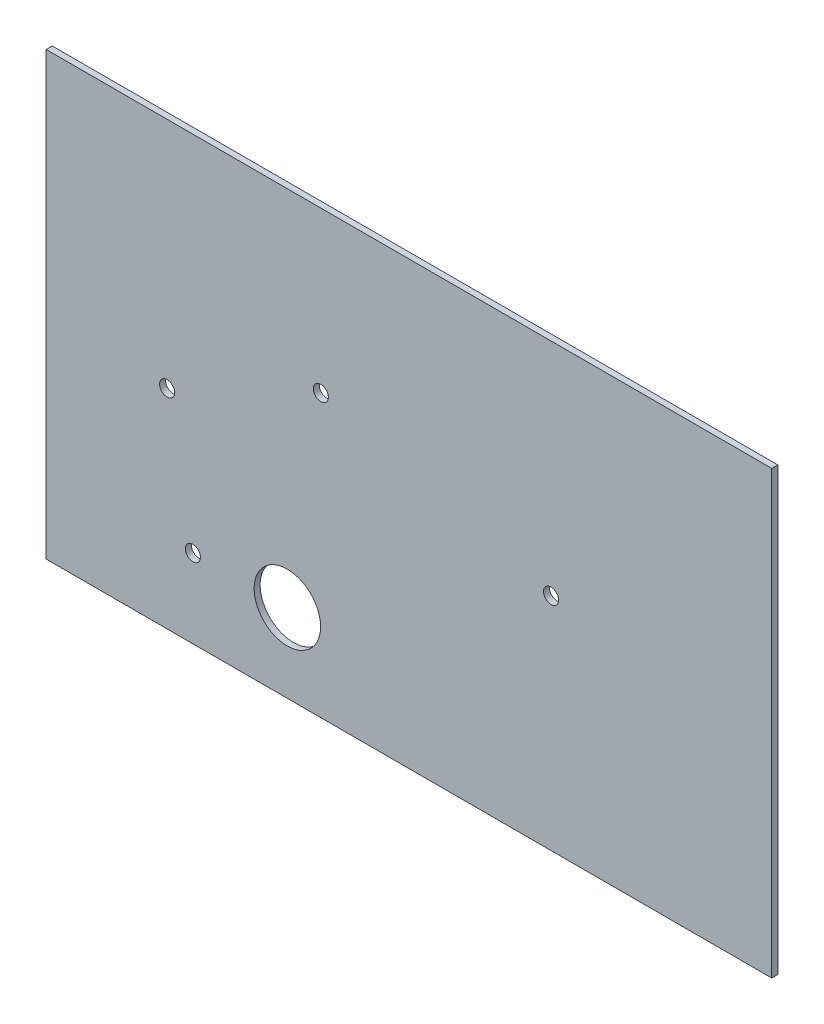
SolidWorks part; units mm, degrees
material "Сталь ШХ15 ГОСТ 801-78"
ref_plane "Plane1" through (0, 0, 0) normal (0, 0, 1) x (1, 0, 0)
ref_plane "Plane2" through (0, 0, 0) normal (0, 1, 0) x (1, 0, 0)
ref_plane "Plane3" through (0, 0, 0) normal (1, 0, 0) x (0, 0, -1)
sketch "Эскиз1" plane through (0, 0, 0) normal (0, 0, 1) x (1, 0, 0)
  line L1 (0, 0) -> (240, 0)
  line L2 (0, 0) -> (0, 146)
  line L3 (0, 146) -> (240, 146)
  line L4 (240, 0) -> (240, 146)
  circle A0 centre (79.7654, 26) radius 11
  circle A1 centre (48.5154, 26) radius 2.5
  circle A4 centre (167, 73) radius 2.5
  circle A5 centre (90.832, 93) radius 2.5
  circle A6 centre (40, 68.9133) radius 2.5
  point P21 (0, 0)
  point P22 (0, 0)
  point P23 (0, 0)
  point P24 (92.6345, 116.3617)
  point P25 (83.75, 36.6044)
  point P26 (85.4232, 27.8066)
  point P27 (0, 0)
  point P28 (83.75, 31.7307)
  point P29 (83.75, 31.089)
  point P30 (112.8716, 31.089)
  point P31 (65.8575, 29.1342)
  point P32 (88.4552, 90)
  point P33 (40, 59.1317)
  point P34 (105.2252, 35.6177)
  point P35 (40, 66.8098)
  point P36 (62.1962, 31.9387)
  dimension "D3" = 22
  dimension "D4" = 78.75
  dimension "D5" = 5
  dimension "D6" = 31.25
  dimension "D9" = 73
  dimension "D7" = 73
  dimension "D1" = 146
  dimension "D2" = 43.75
  dimension "D8" = 26
  dimension "D10" = 56.25
  dimension "D11" = 40
  dimension "D12" = 53
  dimension "D13" = 26
  dimension "D14" = 240
extrude "Бобышка-Вытянуть1" add sketch "Эскиз1" along normal blind 2 contours L2 A0 A1 A4 L4 L3 | L2 L1 L4 A4 A1 A0 region at (120.5182, 73.5343, 0)
